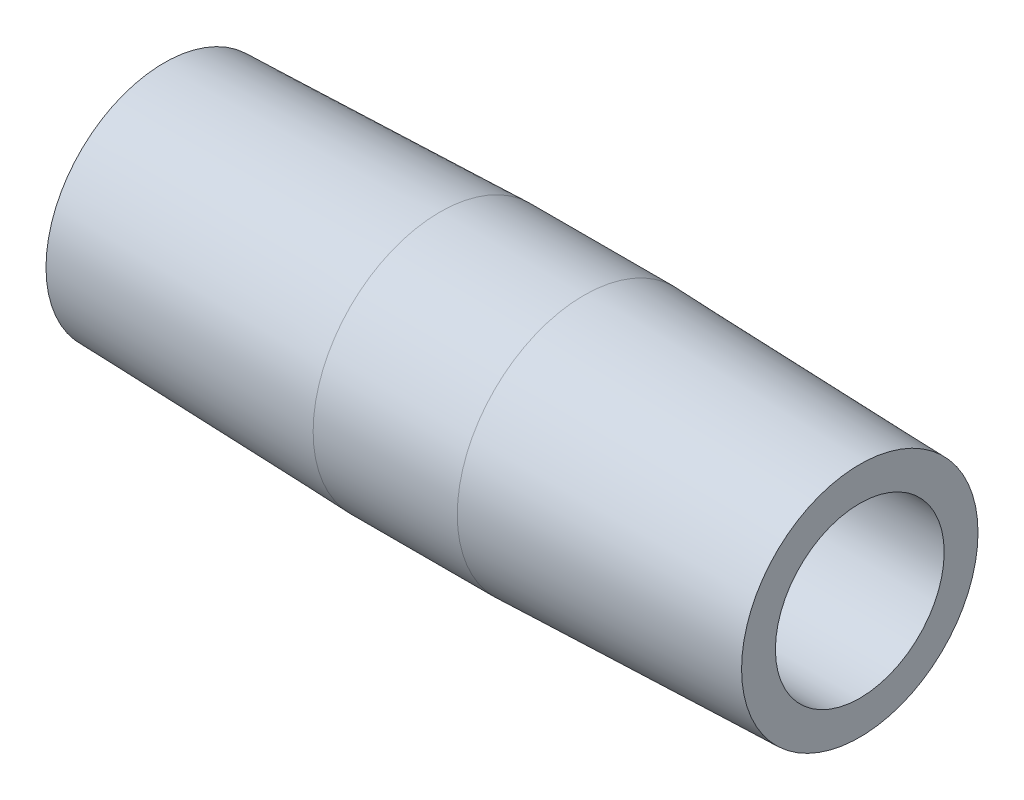
SolidWorks part; units mm, degrees
material "Chrome Stainless Steel"
ref_plane "Front Plane" through (0, 0, 0) normal (0, 0, 1) x (1, 0, 0)
ref_plane "Top Plane" through (0, 0, 0) normal (0, 1, 0) x (1, 0, 0)
ref_plane "Right Plane" through (0, 0, 0) normal (1, 0, 0) x (0, 0, -1)
sketch "Sketch1" plane through (0, 0, 0) normal (0, 0, 1) x (1, 0, 0)
  line L0 (-19.05, 0) -> (19.05, 0) construction
  line L1 (19.05, 6.9453) -> (19.05, -6.9453) construction
  line L2 (-19.05, 6.9453) -> (-19.05, -6.9453) construction
  point P6 (3.9472, 0)
  point P8 (-3.9472, 0)
  point P9 (-3.9472, 6.9453)
  point P10 (-3.9472, -6.9453)
  point P11 (3.9472, 6.9453)
  point P12 (3.9472, -6.9453)
  point P13 (10.2972, 6.9453)
  point P14 (10.2972, -6.9453)
  dimension "D1" = 13.8906
  dimension "D" = 38.1
  dimension "D2" = 15.1028
  dimension "D3" = 6.35
ref_plane "Plane1" through (3.9472, 0, 0) normal (1, 0, 0) x (0, 0, -1)
sketch "Sketch2" plane through (3.9472, 0, 0) normal (1, 0, 0) x (0, 0, -1)
  circle A0 centre (0, 0) radius 6.9453
extrude "Extrude1" add sketch "Sketch2" along normal up to vertex (15.1028 mm away) draft 1.783 up to point (19.05, 0, 0)
sketch "Sketch5" plane through (19.05, 0, 0) normal (1, 0, 0) x (0, 0, -1)
  circle A3 centre (0, 0) radius 4.6228
  dimension "ID" = 9.2456
sketch "Sketch10" plane through (3.9472, 0, 0) normal (-1, 0, 0) x (0, 0, 1)
  circle A0 centre (0, 0) radius 6.598
  dimension "D1" = 13.1961
sketch "Sketch13" plane through (3.9472, 0, 0) normal (-1, 0, 0) x (0, 0, 1)
  circle A1 centre (0, 0) radius 6.598
  circle A2 centre (0, 0) radius 6.598
  dimension "D1" = 0
sketch "Sketch11" plane through (3.9472, 0, 0) normal (-1, 0, 0) x (0, 0, 1)
  circle A0 centre (0, 0) radius 6.9453
  dimension "D1" = 13.8906
extrude "Extrude4" add sketch "Sketch11" along normal up to vertex (3.9472 mm away) separate body up to point (0, 0, 0)
extrude "Extrude5" add sketch "Sketch13" along normal blind 1.0583
mirror "Mirror1" [suppressed] about plane through (0, 0, 0) normal (1, 0, 0) of bodies 112 106
ref_axis "Axis1" through (0, 27.1822, 0) along (0, -1, 0)
pattern_circular "CirPattern1" count 2 over 360 about axis through (0, 27.1822, 0) along (0, -1, 0) of bodies 112
combine bodies "Combine1" operation type add bodies to combine 112 113
extrude "Cut-Extrude3" cut sketch "Sketch5" against normal through all
equation "\"D1@Sketch1\" = \"pipe od@Sketch1\""
equation "\"D2@Sketch1\" = \"R@Sketch1\""
equation "\"D1@Sketch10\" = \"pipe od@Sketch1\"*.95"
equation "\"D1@Sketch11\" = \"pipe od@Sketch1\""
